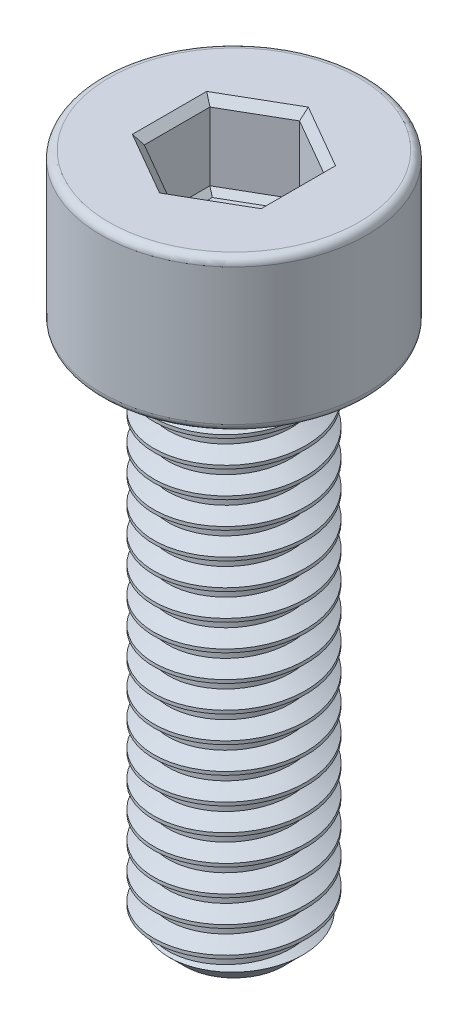
SolidWorks part; units mm, degrees
material "AISI Type A2 Tool Steel"
ref_plane "Front Plane" through (0, 0, 0) normal (0, 0, 1) x (1, 0, 0)
ref_plane "Top Plane" through (0, 0, 0) normal (0, 1, 0) x (1, 0, 0)
ref_plane "Right Plane" through (0, 0, 0) normal (1, 0, 0) x (0, 0, -1)
sketch "Sketch1" plane through (0, 0, 0) normal (0, 1, 0) x (1, 0, 0)
  circle A0 centre (0, 0) radius 2
  dimension "D1" = 4
extrude "Boss-Extrude1" add sketch "Sketch1" along normal blind 14
thread "Thread1" pitch 0.7 start angle 0, offset 1, length 0, pitch 0.7, diameter 4
ref_plane "Plane1" through (2, -1, 0) normal (0, 0, 1) x (1, 0, 0)
sketch "Thread Profile1" plane through (2, -1, 0) normal (0, 0, 1) x (1, 0, 0)
  line L0 (0, 0) -> (0, 0.7) construction
  line L11 (0, 0) -> (0, 0.6125)
  line L12 (0, 0.6125) -> (-0.3789, 0.3937)
  line L13 (-0.3789, 0.3937) -> (-0.3789, 0.2187)
  line L15 (-0.3789, 0.2187) -> (0, 0)
  line L17 (-0.3789, 0.3062) -> (0, 0.3062) construction
  point P2 (0, 0)
  dimension "Pitch" = 0.7
  dimension "Profile_Angle" = 60
  dimension "Profile_Land" = 0.175
  dimension "Profile_Height" = 0.3789
sketch "Sketch4" plane through (0, 14, 0) normal (0, -1, 0) x (-1, 0, 0)
  circle A0 centre (0, 0) radius 3.5
  dimension "D1" = 7
extrude "Boss-Extrude2" add sketch "Sketch4" against normal blind 4
fillet "Fillet1" radius 0.2 2 edges at (0, 14, -3.5) (0, 18, -3.5)
sketch "Sketch6" plane through (0, 0, 0) normal (0, 0, 1) x (1, 0, 0)
  line L0 (0, 0) -> (2.01, 0) construction
  line L1 (2.01, 0) -> (2.01, 0.7)
  line L2 (2.01, 0.7) -> (1.31, 0)
  line L3 (1.31, 0) -> (2.01, 0)
  line L4 (0, 0) -> (0, 0.3482) construction
  dimension "D1" = 0.7
  dimension "D2" = 45
  dimension "D3" = 2.01
revolve "Cut-Revolve1" cut sketch "Sketch6" angle 360 about L4
sketch "Sketch7" plane through (0, 18, 0) normal (0, 1, 0) x (1, 0, 0)
  line L1 (0, 1.7321) -> (-1.5, 0.866)
  line L2 (-1.5, 0.866) -> (-1.5, -0.866)
  line L3 (-1.5, -0.866) -> (0, -1.7321)
  line L4 (0, -1.7321) -> (1.5, -0.866)
  line L5 (1.5, -0.866) -> (1.5, 0.866)
  line L6 (1.5, 0.866) -> (0, 1.7321)
  circle A0 centre (0, 0) radius 1.5 construction
  dimension "D1" = 3
extrude "Cut-Extrude1" cut sketch "Sketch7" against normal blind 2
chamfer "Chamfer1" distance 0.2 angle 45 6 edges at (-1.5, 18, 0) (-0.75, 18, 1.299) (0.75, 18, 1.299) (1.5, 18, 0) (0.75, 18, -1.299) (-0.75, 18, -1.299)
sketch "Sketch8" plane through (0, 16, 0) normal (0, 1, 0) x (1, 0, 0)
  line L1 (0, 1.7321) -> (-1.5, 0.866)
  line L2 (-1.5, 0.866) -> (-1.5, -0.866)
  line L3 (-1.5, -0.866) -> (0, -1.7321)
  line L4 (0, -1.7321) -> (1.5, -0.866)
  line L5 (1.5, -0.866) -> (1.5, 0.866)
  line L6 (1.5, 0.866) -> (0, 1.7321)
  circle A0 centre (0, 0) radius 1.5 construction
extrude "Cut-Extrude2" cut sketch "Sketch8" against normal blind 0.15 draft 45
